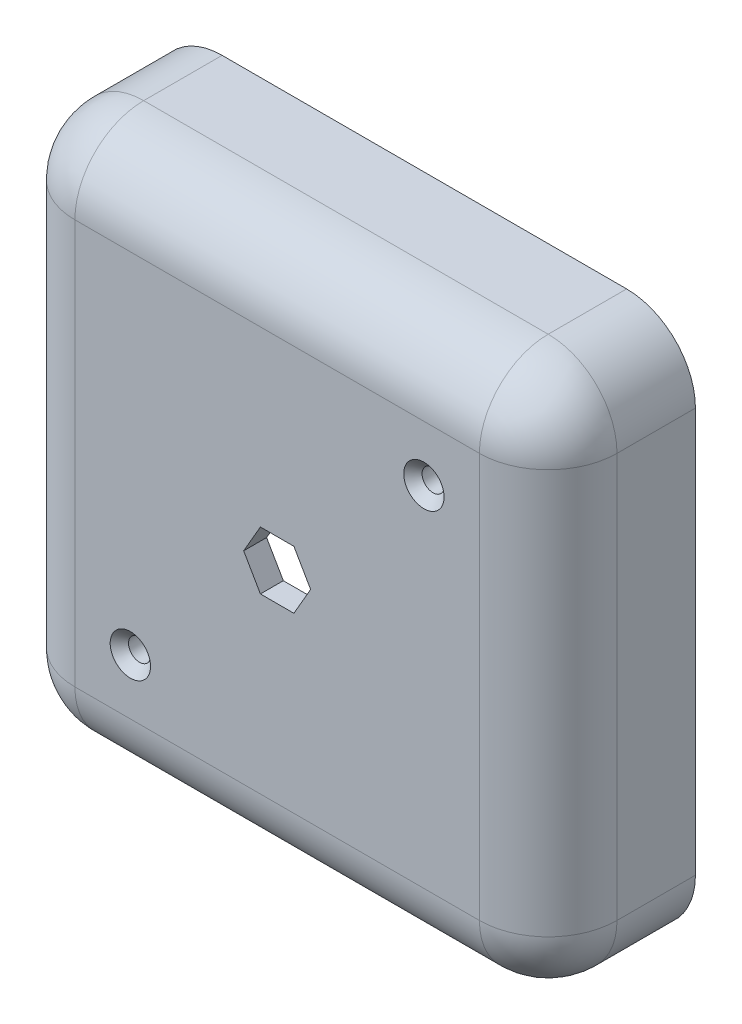
SolidWorks part; units mm, degrees
note: '?' marks a value the reader was unsure of.
ref_plane "Front Plane" through (0, 0, 0) normal (0, 0, 1) x (1, 0, 0)
ref_plane "Top Plane" through (0, 0, 0) normal (0, 1, 0) x (1, 0, 0)
ref_plane "Right Plane" through (0, 0, 0) normal (1, 0, 0) x (0, 0, -1)
sketch "Sketch1" plane through (0, 0, 0) normal (0, 0, 1) x (1, 0, 0)
  line L0 (0, 78.4471) -> (0, -76.9705) construction
  line L1 (-83.0616, 0) -> (77.155, 0) construction
  line L3 (-29.55, 29.55) -> (29.55, 29.55)
  line L4 (-29.55, 29.55) -> (-29.55, -29.55)
  line L5 (-29.55, -29.55) -> (29.55, -29.55)
  line L6 (29.55, 29.55) -> (29.55, -29.55)
  dimension "D1" = 59.1
  dimension "D2" = 59.1
extrude "Boss-Extrude1" add sketch "Sketch1" along normal blind 59.1
ref_plane "Plane1" through (0, -14.775, 14.775) normal (0, -0.7071, 0.7071) x (1, 0, 0)
ref_axis "Axis1" through (-29.55, 29.55, 59.1) along (0.5774, -0.5774, -0.5774)?
ref_plane "Plane2" through (0, 0, 0) normal (-0.5774, -0.5774, 0.5774) x (0.8165, -0.4082, 0.4082)
ref_plane "Plane3" through (-19.7, -19.7, 19.7) normal (0.5774, 0.5774, -0.5774) x (-0.8165, 0.4082, -0.4082)
ref_plane "Plane4" through (-9.85, -9.85, 9.85) normal (-0.5774, -0.5774, 0.5774) x (0.8165, -0.4082, 0.4082)
ref_plane "Plane6" through (0, 0, 29.55) normal (0, 0, -1) x (-1, 0, 0)
ref_plane "Plane10" through (0, 0, 29.55) normal (0, 0, -1) x (-1, 0, 0)
ref_plane "Plane11" through (0, 0, 39.55) normal (0, 0, -1) x (-1, 0, 0)
sketch "Sketch2" plane through (30.721, 30.721, 39.55) normal (0, 0, -1) x (0.2588, -0.9659, 0)
  line L1 (70.2131, 88.1225) -> (-26.7023, 88.1225)
  line L2 (70.2131, 88.1225) -> (70.2131, -10.9923)
  line L3 (70.2131, -10.9923) -> (-26.7023, -10.9923)
  line L4 (-26.7023, 88.1225) -> (-26.7023, -10.9923)
extrude "Cut-Extrude1" cut sketch "Sketch2" along normal through all and the other way blind 3.5
ref_plane "Plane5" through (-39.4, -39.4, 39.4) normal (-0.5774, -0.5774, 0.5774) x (-0.8165, 0.4082, -0.4082)
fillet "Fillet1" radius 7.5 8 edges at (0, -29.55, 59.1) (29.55, 0, 59.1) (29.55, -29.55, 51.075) (-29.55, -29.55, 51.075) (-29.55, 0, 59.1) (0, 29.55, 59.1) (-29.55, 29.55, 51.075) (29.55, 29.55, 51.075)
shell "Shell1" thickness 2.5
sketch "Sketch15" plane through (-29.55, 0, 0) normal (-1, 0, 0) x (0, 0, 1)
  line L0 (51.6, -29.55) -> (21.5731, -29.55)
  line L1 (21.5731, -38.8746) -> (70.3108, -38.8746)
  line L2 (70.3108, -38.8746) -> (70.3108, -22.05)
  line L3 (70.3108, -22.05) -> (59.1, -22.05)
  line L4 (21.5731, -38.8746) -> (21.5731, -29.55)
  arc A0 (51.6, -29.55) -> (59.1, -22.05) centre (51.6, -22.05) ccw
hole_wizard "CSK SLOT for M2 Countersunk Flat Head Screw1" positions "Sketch18" profile "Sketch19" size "M2" standard "ISO" slot yes end condition through all
sketch "Sketch18" plane through (0, 0, 59.1) normal (0, 0, 1) x (1, 0, 0)
  line L4 (55, 0) -> (-55, 0) construction
  line L5 (0, -55) -> (0, 55) construction
  point P0 (16, 16)
  point P9 (19.893, -96.8354)
  point P17 (-16, -16)
  dimension "D1" = 16
  dimension "D2" = 16
  dimension "D3" = 16
  dimension "D4" = 16
sketch "Sketch19" plane through (16, 16, 59.1) normal (1, 0, 0) x (0, -1, 0)
  line L0 (0, 0) -> (0, 16.05)
  line L1 (0, 16.05) -> (1.2, 16.05)
  line L2 (1.2, 16.05) -> (1.2, 1)
  line L3 (1.2, 1) -> (2.2, 0)
  line L5 (2.2, 0) -> (0, 0)
  line L6 (-1.2, 1) -> (-2.2, 0) construction
  line L11 (0, -6.35) -> (0, 107.95) construction
  dimension "Thru Hole Dia." = 2.4
  dimension "Thru Hole Depth" = 16.05
  dimension "Near C'Sink Dia." = 4.4
  dimension "Near C'Sink Angle" = 90
sketch "Sketch20" plane through (0, 0, 59.1) normal (0, 0, 1) x (1, 0, 0)
  line L0 (22.05, 22.05) -> (-22.05, 22.05) construction
  line L1 (-1.825, -3.161) -> (1.825, -3.161)
  line L2 (1.825, -3.161) -> (3.65, 0)
  line L3 (3.65, 0) -> (1.825, 3.161)
  line L4 (1.825, 3.161) -> (-1.825, 3.161)
  line L5 (-1.825, 3.161) -> (-3.65, 0)
  line L6 (-3.65, 0) -> (-1.825, -3.161)
  line L7 (-1.825, -3.161) -> (1.825, 3.161) construction
  point P0 (0, 0)
  dimension "D1" = 3.65
extrude "Cut-Extrude2" cut sketch "Sketch20" against normal through all
